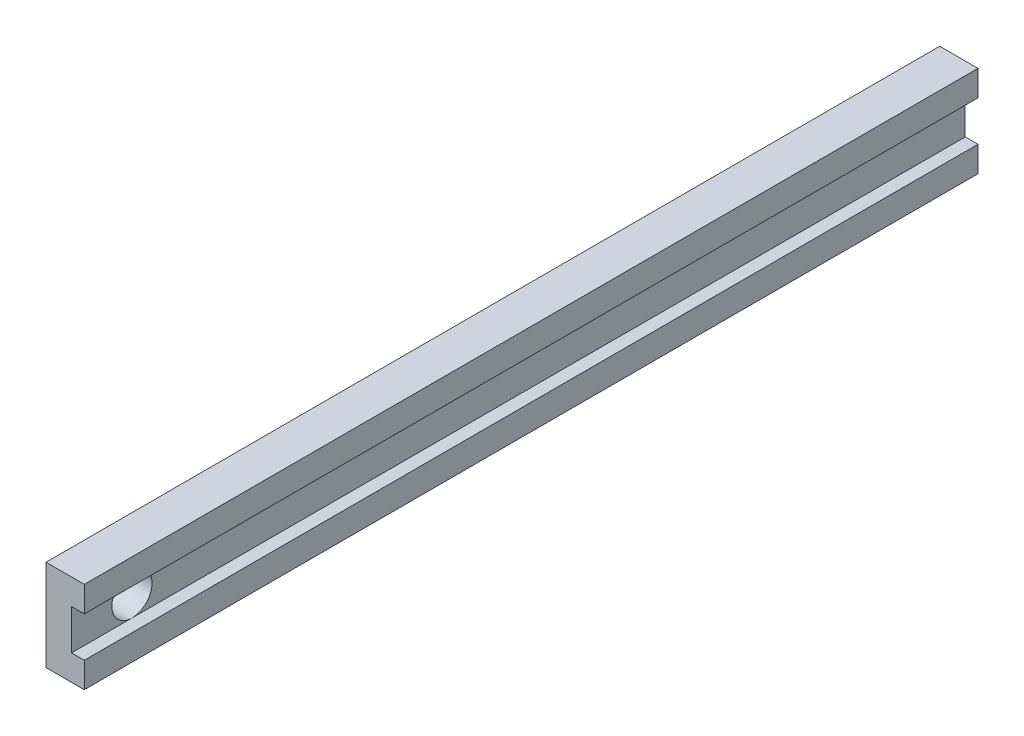
SolidWorks part; units mm, degrees
ref_plane "Front Plane" through (0, 0, 0) normal (0, 0, 1) x (1, 0, 0)
ref_plane "Top Plane" through (0, 0, 0) normal (0, 1, 0) x (1, 0, 0)
ref_plane "Right Plane" through (0, 0, 0) normal (1, 0, 0) x (0, 0, -1)
sketch "Sketch1" plane through (0, 0, 0) normal (0, 0, 1) x (1, 0, 0)
  line L0 (0, -5.3188) -> (0, -13.3188)
  line L1 (0, -13.3188) -> (2.54, -13.3188)
  line L2 (2.54, -13.3188) -> (2.54, -18.3988)
  line L3 (2.54, -18.3988) -> (-5.08, -18.3988)
  line L4 (-5.08, -18.3988) -> (-5.08, -0.2388)
  line L5 (-5.08, -0.2388) -> (2.54, -0.2388)
  line L6 (2.54, -0.2388) -> (2.54, -5.3188)
  line L7 (2.54, -5.3188) -> (0, -5.3188)
  dimension "D1" = 5.08
  dimension "D2" = 8
  dimension "D3" = 5.08
  dimension "D4" = 2.54
extrude "Boss-Extrude1" add sketch "Sketch1" along normal blind 177.8
hole_wizard "Ø8.0mm Dowel Hole1" positions "Sketch2" profile "Sketch3" hole size "Ø8.0" standard "ANSI Metric" end condition through all
sketch "Sketch2" plane through (-5.08, 0, 0) normal (-1, 0, 0) x (0, 0, 1)
  line L0 (165.7819, -0.2388) -> (165.7819, -18.3988) construction
  line L1 (177.8, -0.2388) -> (0, -0.2388) construction
  line L2 (177.8, -18.3988) -> (0, -18.3988) construction
  point P0 (165.7819, -9.3188)
  point P10 (0, 0)
sketch "Sketch3" plane through (-5.08, -9.3188, 165.7819) normal (0, 1, 0) x (0, 0, 1)
  line L0 (0, 0) -> (0, 7.62)
  line L1 (0, 7.62) -> (4, 7.62)
  line L2 (4, 7.62) -> (4, 0)
  line L5 (4, 0) -> (0, 0)
  line L11 (0, -6.35) -> (0, 107.95) construction
  dimension "Thru Hole Dia." = 8
  dimension "Thru Hole Depth" = 7.62
